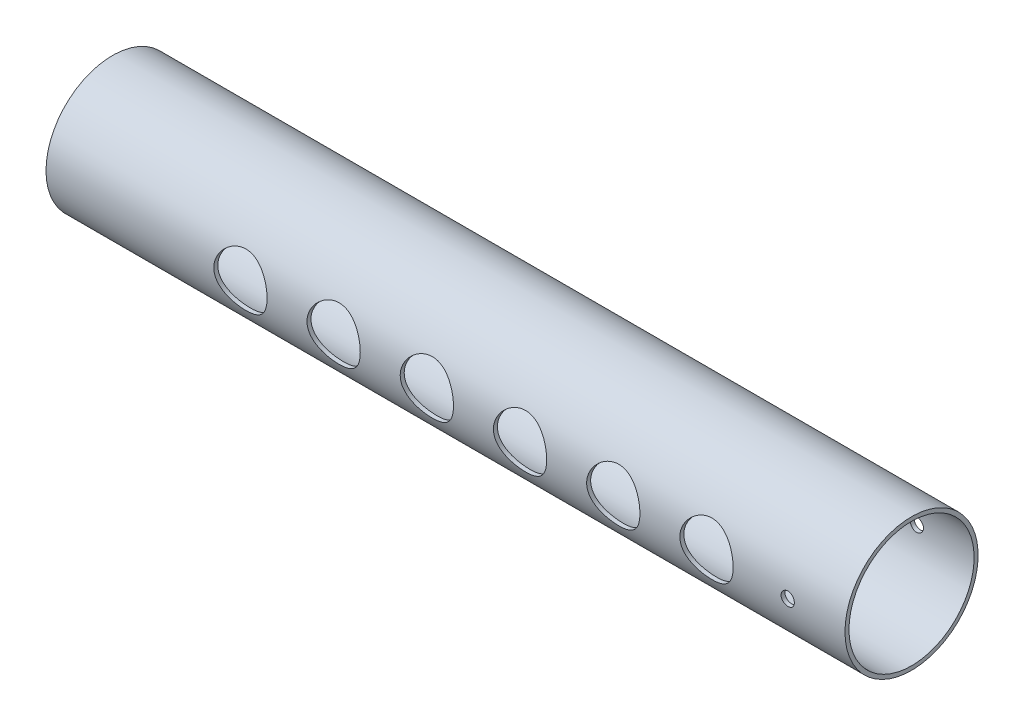
SolidWorks part; units mm, degrees
note: The reader was unsure of these and kept them because the rebuilt part matched: shared geometry of "Croquis2<3>".
ref_plane "alzado" through (0, 0, 0) normal (0, 0, 1) x (1, 0, 0)
ref_plane "Planta" through (0, 0, 0) normal (0, 1, 0) x (1, 0, 0)
ref_plane "Vista lateral" through (0, 0, 0) normal (1, 0, 0) x (0, 0, -1)
sketch "Croquis2" plane through (0, 0, 0) normal (0, 0, 1) x (1, 0, 0)
  line L0 (0, 0) -> (-300, 0)
  circle A0 centre (-52, 0) radius 10
  circle A1 centre (-87, 0) radius 10
  circle A2 centre (-122, 0) radius 10
  circle A3 centre (-157, 0) radius 10
  circle A4 centre (-192, 0) radius 10
  circle A5 centre (-227, 0) radius 10
  dimension "D1" = 52
  dimension "D2" = 35
  dimension "D3" = 35
other "Miembro estructural1" corner treatment miter
ref_plane "Plano3" through (0, 0, 0) normal (-1, 0, 0) x (0, -1, 0)
sketch "Sketch110" plane through (0, 0, 0) normal (-1, 0, 0) x (0, -1, 0)
  circle A0 centre (0, 0) radius 23.5
  circle A1 centre (0, 0) radius 25
  point P3 (0, 0)
  dimension "In_dia" = 47
  dimension "Out_dia" = 50
extrude "Cortar-Extruir1" cut sketch "Croquis2" against normal through all both and the other way through all contours A0
extrude "Cortar-Extruir2" cut sketch "Croquis2<3>" against normal through all both and the other way through all contours A1 | A2 | A3 | A4 | A5
sketch "Croquis2<3>" plane through (0, 0, 0) normal (0, 0, 1) x (1, 0, 0) same geometry as "Croquis2"
sketch "Croquis3" plane through (0, 0, 0) normal (0, 0, 1) x (1, 0, 0)
  line L0 (0, 0) -> (-300, 0) construction
  line L1 (-300, 25) -> (-300, -25) construction
  circle A0 centre (-21.5081, 0) radius 2.5
extrude "Cortar-Extruir3" cut sketch "Croquis3" against normal through all both and the other way through all
